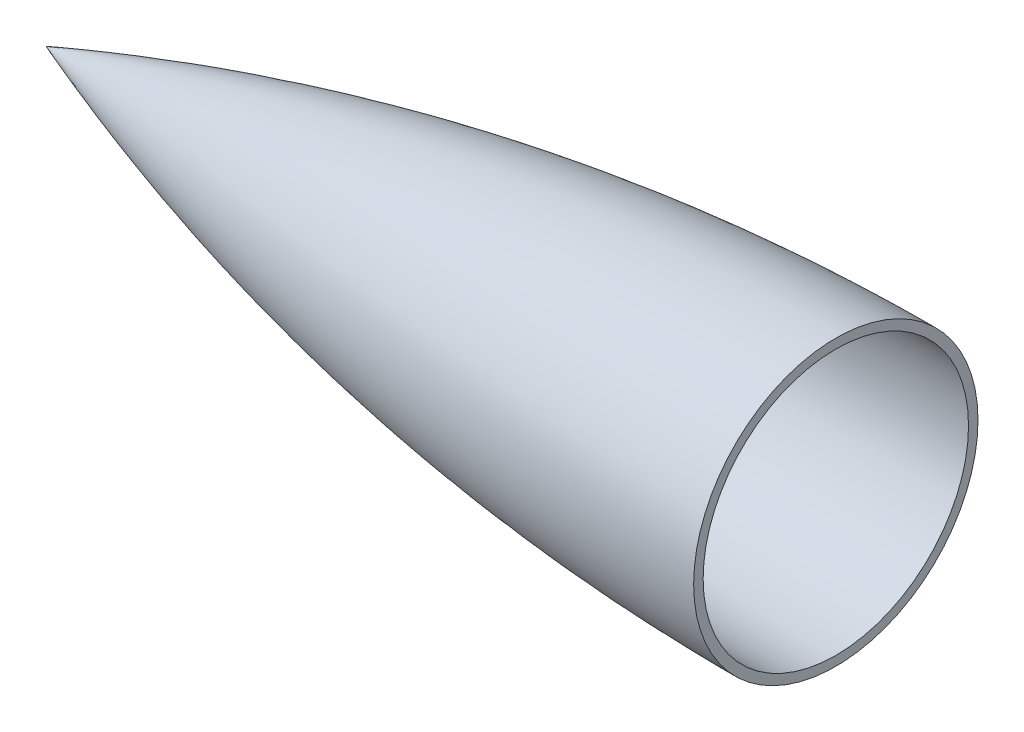
SolidWorks part; units mm, degrees
material "Hexcel AS4C (3000 Filaments)"
ref_plane "Plan de face" through (0, 0, 0) normal (0, 0, 1) x (1, 0, 0)
ref_plane "Plan de dessus" through (0, 0, 0) normal (0, 1, 0) x (1, 0, 0)
ref_plane "Plan de droite" through (0, 0, 0) normal (1, 0, 0) x (0, 0, -1)
sketch "Esquisse1" plane through (0, 0, 0) normal (0, 1, 0) x (1, 0, 0)
  line L0 (0, 0) -> (301.6119, 0) construction
  line L1 (250, 45) -> (250, 0)
  line L2 (250, 0) -> (0, 0) construction
  line L3 (250, 0) -> (0, 0)
  line L4 (-54.2063, 0) -> (320.9698, 0) construction
  spline S0 degree 4 poles (-23.75, -9.3206) (-23.3793, -9.1675) (-22.6378, -8.8618) (-21.1533, -8.2524) (-18.9254, -7.3456) (-16.3195, -6.2962) (-13.3492, -5.1155) (-10.3763, -3.9492) (-7.7868, -2.9463) (-5.5576, -2.0927) (-3.7137, -1.3926) (-2.2648, -0.8461) (-0.1075, -0.0388) (0.8923, 0.3317) (3.5178, 1.3014) (4.8595, 1.7876) (6.481, 2.3772) (7.8299, 2.8619) (9.2895, 3.3843) (11.7855, 4.2708) (14.6616, 5.279) (17.8907, 6.3927) (22.2119, 7.856) (26.5382, 9.2938) (31.5993, 10.9361) (37.3979, 12.7636) (43.2125, 14.542) (49.0415, 16.271) (56.3462, 18.3703) (65.1397, 20.7903) (73.9667, 23.0858) (82.8251, 25.2563) (90.227, 26.9814) (96.16, 28.3112) (103.5901, 29.9105) (112.5275, 31.7288) (121.4898, 33.4206) (130.475, 34.9856) (139.4772, 36.4488) (148.4954, 37.8102) (157.5322, 39.0439) (166.5854, 40.1499) (174.1395, 40.9861) (180.1882, 41.6038) (186.242, 42.1702) (192.3004, 42.6852) (197.6051, 43.0908) (202.1542, 43.4064) (205.9467, 43.648) (208.9814, 43.8283) (212.0168, 43.9958) (215.053, 44.1504) (218.0897, 44.2922) (221.1271, 44.4211) (224.165, 44.5371) (227.2032, 44.6402) (230.242, 44.7304) (233.281, 44.8077) (235.9407, 44.8641) (238.2201, 44.9044) (240.1205, 44.9326) (241.6389, 44.9519) (243.1631, 44.968) (244.6703, 44.9809) (246.2317, 44.9906) (247.6173, 44.997) (249.5342, 45.0003) (250.4911, 45.0003) (252.4435, 44.9969) (253.8441, 44.9902) (255.4491, 44.9801) (256.9849, 44.9666) (258.9327, 44.9456) (261.2684, 44.9135) (264.0075, 44.866) (267.1406, 44.7979) (269.8924, 44.7261) (272.2495, 44.6559) (273.8214, 44.6045) (274.6071, 44.5777) (275, 44.564) knots 0 0 0 0 0 0.005245 0.010489 0.020979 0.031468 0.041958 0.052322 0.062685 0.067867 0.073049 0.078231 0.083413 0.093352 0.098321 0.10329 0.108259 0.113229 0.118198 0.123167 0.143044 0.152983 0.162922 0.182799 0.202676 0.222553 0.24243 0.262307 0.282185 0.321939 0.361693 0.38157 0.401447 0.421325 0.441202 0.480956 0.52071 0.540588 0.560465 0.600219 0.639973 0.65985 0.679728 0.699605 0.719482 0.739359 0.759236 0.769175 0.779113 0.789052 0.798991 0.808929 0.818868 0.828806 0.838745 0.848683 0.858622 0.868561 0.878499 0.883468 0.888438 0.893407 0.898376 0.903346 0.908315 0.913284 0.918253 0.923331 0.928409 0.933486 0.938564 0.943642 0.948719 0.958874 0.969156 0.979437 0.989719 0.994859 1 1 1 1 1 construction
  spline S1 degree 4 poles (0, 0) (0.5947, 0.2212) (1.4352, 0.5323) (3.5178, 1.3014) (4.8595, 1.7876) (6.481, 2.3772) (7.8299, 2.8619) (9.2895, 3.3843) (11.7855, 4.2708) (14.6616, 5.279) (17.8907, 6.3927) (22.2119, 7.856) (26.5382, 9.2938) (31.5993, 10.9361) (37.3979, 12.7636) (43.2125, 14.542) (49.0415, 16.271) (56.3462, 18.3703) (65.1397, 20.7903) (73.9667, 23.0858) (82.8251, 25.2563) (90.227, 26.9814) (96.16, 28.3112) (103.5901, 29.9105) (112.5275, 31.7288) (121.4898, 33.4206) (130.475, 34.9856) (139.4772, 36.4488) (148.4954, 37.8102) (157.5322, 39.0439) (166.5854, 40.1499) (174.1395, 40.9861) (180.1882, 41.6038) (186.242, 42.1702) (192.3004, 42.6852) (197.6051, 43.0908) (202.1542, 43.4064) (205.9467, 43.648) (208.9814, 43.8283) (212.0168, 43.9958) (215.053, 44.1504) (218.0897, 44.2922) (221.1271, 44.4211) (224.165, 44.5371) (227.2032, 44.6402) (230.242, 44.7304) (233.281, 44.8077) (235.9407, 44.8641) (238.2201, 44.9044) (240.1205, 44.9326) (241.6389, 44.9519) (243.1631, 44.968) (244.6703, 44.9809) (246.2317, 44.9906) (247.6173, 44.997) (249.0472, 44.9995) (249.6828, 45) (250, 45) knots 0.083413 0.083413 0.083413 0.083413 0.083413 0.093352 0.098321 0.10329 0.108259 0.113229 0.118198 0.123167 0.143044 0.152983 0.162922 0.182799 0.202676 0.222553 0.24243 0.262307 0.282185 0.321939 0.361693 0.38157 0.401447 0.421325 0.441202 0.480956 0.52071 0.540588 0.560465 0.600219 0.639973 0.65985 0.679728 0.699605 0.719482 0.739359 0.759236 0.769175 0.779113 0.789052 0.798991 0.808929 0.818868 0.828806 0.838745 0.848683 0.858622 0.868561 0.878499 0.883468 0.888438 0.893407 0.898376 0.903346 0.908315 0.913284 0.918253 0.918253 0.918253 0.918253 0.918253
  dimension "D1" = 250
  dimension "D2" = 45
revolve "Révolution1" add sketch "Esquisse1" angle 360 about L3
shell "Coque4" thickness 3 removed face at (250, 0, -45)
